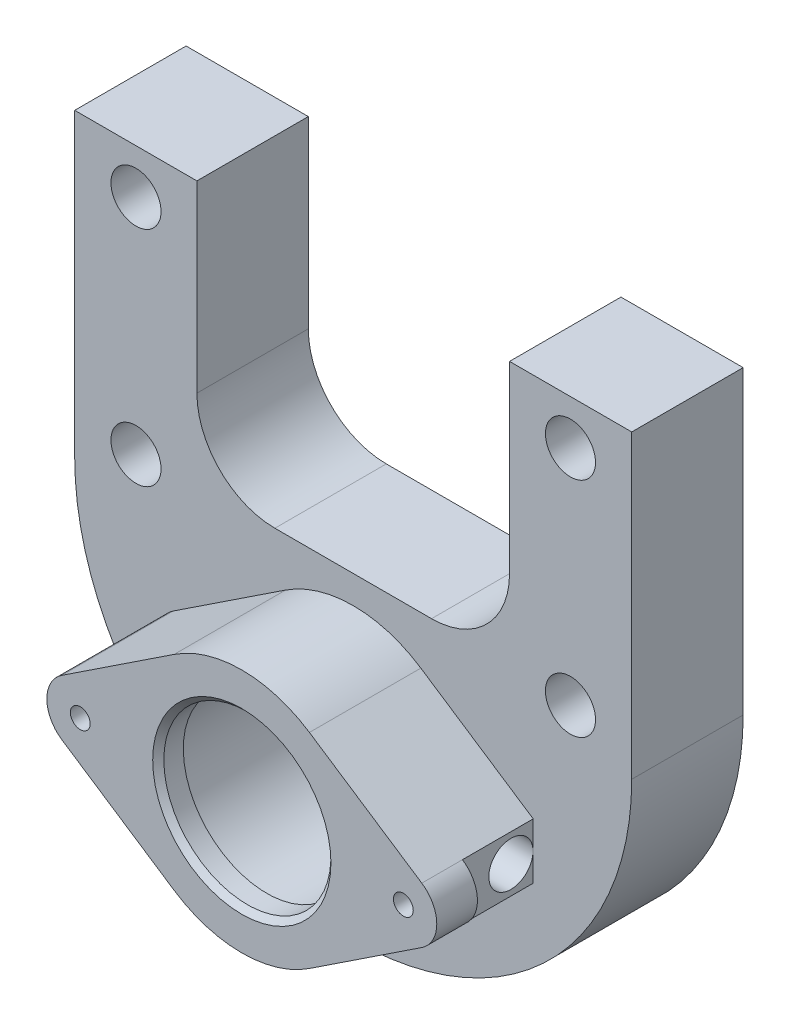
SolidWorks part; units mm, degrees
material "AISI 316 Annealed Stainless Steel Bar (SS)"
ref_plane "Front" through (0, 0, 0) normal (0, 0, 1) x (1, 0, 0)
ref_plane "Top" through (0, 0, 0) normal (0, 1, 0) x (1, 0, 0)
ref_plane "Right" through (0, 0, 0) normal (1, 0, 0) x (0, 0, -1)
sketch "Sketch1" plane through (0, 0, 0) normal (0, 0, 1) x (1, 0, 0)
  line L0 (0, 37) -> (0, 0) construction
  line L1 (-25, -15) -> (25, -15)
  line L2 (-25, -15) -> (-25, 37)
  line L3 (-25, 37) -> (25, 37)
  line L4 (25, -15) -> (25, 37)
  circle A0 centre (0, 0) radius 9.5 construction
  dimension "D3" = 19
  dimension "D5" = 15
  dimension "D1" = 52
  dimension "D2" = 50
extrude "Boss-Extrude1" add sketch "Sketch1" along normal blind 20
sketch "Sketch3" plane through (0, 0, 0) normal (1, 0, 0) x (0, 0, -1)
  line L0 (0, 0) -> (-20, 0)
  line L1 (-20, 0) -> (-20, 7.5)
  line L2 (-20, 7.5) -> (-17.75, 7.5)
  line L3 (-17.75, 7.5) -> (-17.75, 8)
  line L4 (-17.75, 8) -> (-7, 8)
  line L5 (-7, 8) -> (-7, 11)
  line L6 (-7, 11) -> (0, 11)
  line L7 (0, 37) -> (0, 0) construction
  line L8 (0, 11) -> (0, 0)
  line L9 (-20, -15) -> (-20, 37) construction
  dimension "D1" = 11
  dimension "D2" = 8
  dimension "D3" = 7.5
  dimension "D4" = 7
  dimension "D5" = 2.25
revolve "Cut-Revolve1" cut sketch "Sketch3" angle 360 about L0
hole_wizard "5/32 (0.15625) Diameter Hole1" positions "Sketch4" profile "Sketch5" hole size "5/32" standard "ANSI Inch" end condition up to next
sketch "Sketch4" plane through (25, 0, 0) normal (1, 0, 0) x (0, 0, -1)
  line L1 (0, 0) -> (-20, 0) construction
  line L2 (-20, -15) -> (-20, 37) construction
  point P0 (-12, 0)
  dimension "D1" = 8
sketch "Sketch5" plane through (25, 0, 12) normal (0, 1, 0) x (0, 0, -1)
  line L0 (0, 0) -> (0, 17)
  line L1 (0, 17) -> (1.9844, 17)
  line L2 (1.9844, 17) -> (1.9844, 0)
  line L5 (1.9844, 0) -> (0, 0)
  line L11 (0, -6.35) -> (0, 107.95) construction
  dimension "Thru Hole Dia." = 3.9688
  dimension "Thru Hole Depth" = 17
fillet "Fillet1" radius 5 1 edges at (0, 37, 20) profile chamfer
hole_wizard "#2-56 Tapped Hole1" positions "Sketch8" profile "Sketch9" tap size "#2-56" standard "ANSI Inch"
sketch "Sketch8" plane through (0, 0, 20) normal (0, 0, 1) x (1, 0, 0)
  line L0 (-14.5, 0) -> (14.5, 0)
  point P0 (-14.5, 0)
  point P2 (14.5, 0)
  dimension "D1" = 29
sketch "Sketch9" plane through (-14.5, 0, 20) normal (1, 0, 0) x (0, -1, 0)
  line L0 (0, 0) -> (0, 8.4542)
  line L1 (0, 8.4542) -> (0.889, 7.92)
  line L2 (0.889, 7.92) -> (0.889, 0)
  line L5 (0.889, 0) -> (0, 0)
  line L10 (0, 8.4542) -> (-0.889, 7.92) construction
  line L11 (0, -6.35) -> (0, 107.95) construction
  dimension "Tap Drill Dia." = 1.778
  dimension "Tap Drill Depth" = 7.92
  dimension "Drill Angle" = 118
cosmetic thread "Hole Thread1" parameters "D1"=6.2259, "D2"=2.1844
cosmetic thread "Hole Thread2" parameters "D1"=6.555, "D2"=2.1844
sketch "Sketch19" plane through (0, 0, 20) normal (0, 0, 1) x (1, 0, 0)
  line L0 (23.5, 37) -> (23.5, 33)
  line L1 (15.5, 33) -> (15.5, 37)
  line L2 (15.5, 37) -> (23.5, 37)
  line L3 (0, 0) -> (0, 32) construction
  line L4 (25, 32) -> (-25, 32) construction
  line L6 (-25, 37) -> (25, 37) construction
  line L7 (-15.5, 37) -> (-23.5, 37)
  line L8 (-15.5, 33) -> (-15.5, 37)
  line L9 (-23.5, 37) -> (-23.5, 33)
  line L10 (25, 37) -> (25, 32) construction
  arc A0 (23.5, 33) -> (15.5, 33) centre (19.5, 33) cw
  arc A1 (-23.5, 33) -> (-15.5, 33) centre (-19.5, 33) ccw
  dimension "D3" = 4
  dimension "D1" = 5.5
  dimension "D2" = 4
extrude "Cut-Extrude2" cut sketch "Sketch19" against normal blind 10
hole_wizard "#8 Clearance Hole1" positions "Sketch20" profile "Sketch21" hole size "#8" standard "ANSI Inch" end condition through all
sketch "Sketch20" plane through (0, 0, 10) normal (0, 0, 1) x (1, 0, 0)
  point P0 (19.5, 33)
  point P5 (-19.5, 33)
sketch "Sketch21" plane through (19.5, 33, 10) normal (1, 0, 0) x (0, -1, 0)
  line L0 (0, 0) -> (0, 10)
  line L1 (0, 10) -> (2.2479, 10)
  line L2 (2.2479, 10) -> (2.2479, 0)
  line L5 (2.2479, 0) -> (0, 0)
  line L11 (0, -6.35) -> (0, 107.95) construction
  dimension "Thru Hole Dia." = 4.4958
  dimension "Thru Hole Depth" = 10
hole_wizard "CBORE for #8 Socket Head Cap Screw1" positions "Sketch16" profile "Sketch17" counterbore size "#8" standard "ANSI Inch" end condition through all
sketch "Sketch16" plane through (0, 0, 20) normal (0, 0, 1) x (1, 0, 0)
  line L0 (-19.5, 13) -> (-19.5, 33) construction
  line L1 (-19.5, 33) -> (19.5, 33) construction
  line L2 (19.5, 33) -> (19.5, 13) construction
  line L5 (0, 33) -> (0, 37) construction
  line L8 (-25, 32) -> (-25, -15) construction
  line L9 (-15.5, 37) -> (15.5, 37) construction
  point P0 (-19.5, 13)
  point P6 (19.5, 13)
  dimension "D1" = 5.5
  dimension "D2" = 4
  dimension "D3" = 20
sketch "Sketch17" plane through (-19.5, 13, 20) normal (1, 0, 0) x (0, -1, 0)
  line L0 (0, 0) -> (0, 20)
  line L1 (0, 20) -> (2.2479, 20)
  line L3 (2.2479, 20) -> (2.2479, 10)
  line L4 (2.2479, 10) -> (3.9687, 10)
  line L5 (3.9687, 10) -> (3.9687, 0)
  line L7 (3.9687, 0) -> (0, 0)
  line L11 (0, -6.35) -> (0, 107.95) construction
  dimension "Thru Hole Dia." = 4.4958
  dimension "Thru Hole Depth" = 20
  dimension "C'Bore Dia." = 7.9375
  dimension "C'Bore Depth" = 10
hole_wizard "1/8 (0.1250) Dowel Hole1" positions "Sketch10" profile "Sketch11" hole size "1/8" standard "ANSI Inch"
sketch "Sketch10" plane through (0, 0, 0) normal (0, 0, -1) x (-1, 0, 0)
  line L10 (-19.5, 33) -> (-19.5, 13) construction
  point P0 (-19.5, 23)
sketch "Sketch11" plane through (19.5, 23, 0) normal (1, 0, 0) x (0, 1, 0)
  line L0 (0, 0) -> (0, 5.9539)
  line L1 (0, 5.9539) -> (1.5875, 5)
  line L2 (1.5875, 5) -> (1.5875, 0)
  line L5 (1.5875, 0) -> (0, 0)
  line L10 (0, 5.9539) -> (-1.5875, 5) construction
  line L11 (0, -6.35) -> (0, 107.95) construction
  dimension "Hole Dia." = 3.175
  dimension "Hole Depth" = 5
  dimension "Drill Angle" = 118
hole_wizard "1/8 (0.1250) Dowel Slot1" positions "Sketch12" profile "Sketch13" size "1/8" standard "ANSI Inch" slot yes
sketch "Sketch12" plane through (0, 0, 0) normal (0, 0, -1) x (-1, 0, 0)
  line L0 (17.5, 23) -> (21.5, 23) construction
  line L5 (19.5, 13) -> (19.5, 33) construction
  point P0 (19.5, 23)
  dimension "D1" = 4
sketch "Sketch13" plane through (-19.5, 23, 0) normal (1, 0, 0) x (0, 1, 0)
  line L0 (0, 0) -> (0, 5.9539)
  line L1 (0, 5.9539) -> (1.5875, 5)
  line L2 (1.5875, 5) -> (1.5875, 0)
  line L5 (1.5875, 0) -> (0, 0)
  line L10 (0, 5.9539) -> (-1.5875, 5) construction
  line L11 (0, -6.35) -> (0, 107.95) construction
  dimension "Hole Dia." = 3.175
  dimension "Hole Depth" = 5
  dimension "Drill Angle" = 118
sketch "Sketch22" plane through (0, 0, 0) normal (0, 0, -1) x (-1, 0, 0)
  circle A0 centre (0, 0) radius 10
  dimension "D1" = 20
extrude "Cut-Extrude3" [suppressed] cut sketch "Sketch22" along normal blind 1.1 from offset 2 offset against normal yes
chamfer "Chamfer1" distance 0.5 angle 45 2 edges at (0, 11, 0) (0, 7.5, 20)
sketch "Sketch23" plane through (0, 0, 20) normal (0, 0, 1) x (1, 0, 0)
  line L0 (0, 37) -> (0, 30) construction
  line L1 (-7.5313, 30) -> (7.5313, 30)
  line L2 (-13.5313, 24) -> (-13.5313, 19.5)
  line L3 (-7.5313, 13.5) -> (7.5313, 13.5)
  line L4 (13.5313, 24) -> (13.5313, 19.5)
  line L5 (-15.5, 37) -> (15.5, 37) construction
  line L6 (0, 13.5) -> (0, 11.5) construction
  line L7 (25, 37) -> (-25, 37) construction
  circle A1 centre (0, 0) radius 11.5 construction
  circle A3 centre (19.5, 13) radius 3.9688 construction
  arc A4 (-7.5313, 30) -> (-13.5313, 24) centre (-7.5313, 24) ccw
  arc A5 (-13.5313, 19.5) -> (-7.5313, 13.5) centre (-7.5313, 19.5) ccw
  arc A6 (7.5313, 13.5) -> (13.5313, 19.5) centre (7.5313, 19.5) ccw
  arc A7 (7.5313, 30) -> (13.5313, 24) centre (7.5313, 24) cw
  dimension "D2" = 2
  dimension "D3" = 6
  dimension "D1" = 7
  dimension "D4" = 2
extrude "Cut-Extrude4" [suppressed] cut sketch "Sketch23" against normal through all
fillet "Fillet2" [suppressed] radius 25
sketch "Sketch24" plane through (0, 0, 20) normal (0, 0, 1) x (1, 0, 0)
  line L0 (-15.5, 37) -> (15.5, 37) construction
  line L1 (-14.0313, 37) -> (14.0313, 37)
  line L2 (-14.0313, 37) -> (-14.0313, 20.5)
  line L3 (-7.0313, 13.5) -> (7.0313, 13.5)
  line L4 (14.0313, 37) -> (14.0313, 20.5)
  line L5 (0, 13.5) -> (0, 0) construction
  circle A0 centre (-19.5, 13) radius 3.9688 construction
  arc A1 (7.0313, 13.5) -> (14.0313, 20.5) centre (7.0313, 20.5) ccw
  arc A2 (-14.0313, 20.5) -> (-7.0313, 13.5) centre (-7.0313, 20.5) ccw
  circle A4 centre (0, 0) radius 11.5 construction
  dimension "D1" = 1.5
  dimension "D2" = 7
  dimension "D3" = 2
extrude "Cut-Extrude5" cut sketch "Sketch24" against normal through all
fillet "Fillet3" radius 25 2 edges at (25, -15, 10) (-25, -15, 10)
sketch "Sketch27" plane through (0, 0, 20) normal (0, 0, 1) x (1, 0, 0)
  line L0 (-16.1552, 2.5021) -> (-6.069, 9.1743)
  line L1 (6.069, 9.1743) -> (16.1552, 2.5021)
  line L2 (16.1552, -2.5021) -> (6.069, -9.1743)
  line L3 (-6.069, -9.1743) -> (-16.1552, -2.5021)
  arc A0 (-6.069, -9.1743) -> (6.069, -9.1743) centre (0, 0) ccw
  arc A1 (-16.1552, 2.5021) -> (-16.1552, -2.5021) centre (-14.5, 0) ccw
  arc A2 (16.1552, -2.5021) -> (16.1552, 2.5021) centre (14.5, 0) ccw
  arc A3 (6.069, 9.1743) -> (-6.069, 9.1743) centre (0, 0) ccw
  dimension "D1" = 11
  dimension "D2" = 3
extrude "Cut-Extrude6" cut sketch "Sketch27" against normal blind 10 flip side to cut
ref_plane "Plane1" through (17.5, 0, 0) normal (1, 0, 0) x (0, 0, -1)
sketch "Sketch28" plane through (17.5, 0, 0) normal (1, 0, 0) x (0, 0, -1)
  line L0 (-10, 10) -> (-10, -15) construction
  line L1 (-10, 2.5021) -> (-16.35, 2.5021)
  line L2 (-10, 2.5021) -> (-10, -2.5021)
  line L3 (-10, -2.5021) -> (-16.35, -2.5021)
  line L4 (-16.35, 2.5021) -> (-16.35, -2.5021)
  line L5 (-20, 0) -> (-16.35, 0) construction
  line L6 (-20, 2.5021) -> (-20, -2.5021) construction
  line L7 (-10, 2.5021) -> (-20, 2.5021) construction
  line L8 (-10, -2.5021) -> (-20, -2.5021) construction
  dimension "D1" = 6.35
extrude "Cut-Extrude7" cut sketch "Sketch28" against normal up to vertex (1.3448 mm away) up to point (16.1552, 2.5021, 20)
